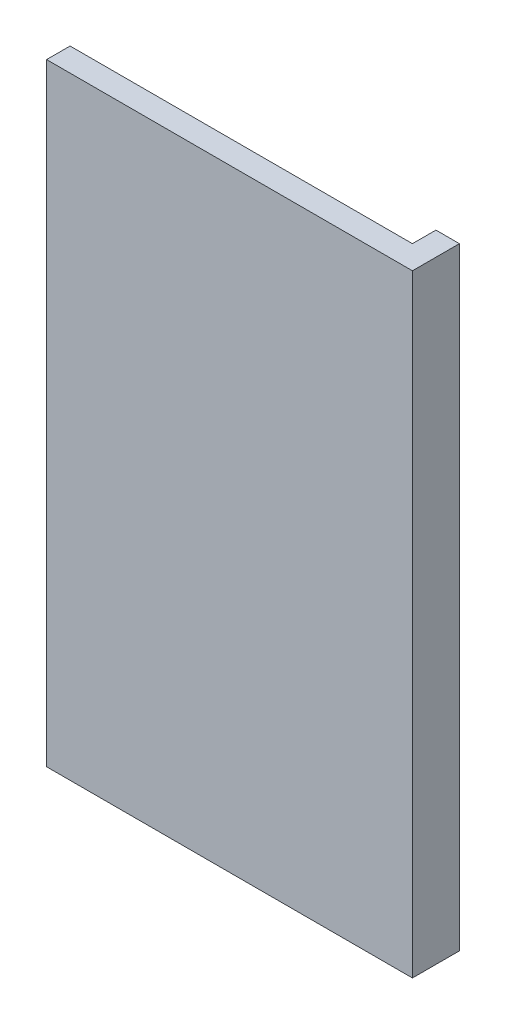
SolidWorks part; units mm, degrees
ref_plane "Front Plane" through (0, 0, 0) normal (0, 0, 1) x (1, 0, 0)
ref_plane "Top Plane" through (0, 0, 0) normal (0, 1, 0) x (1, 0, 0)
ref_plane "Right Plane" through (0, 0, 0) normal (1, 0, 0) x (0, 0, -1)
other "Configuration Table"
sketch "Sketch2" plane through (0, 0, 0) normal (0, 0, 1) x (1, 0, 0)
  line L1 (15.3819, 48) -> (-13.6181, 48)
  line L2 (15.3819, 48) -> (15.3819, -2)
  line L3 (15.3819, -2) -> (-13.6181, -2)
  line L4 (-13.6181, 48) -> (-13.6181, -2)
  line L5 (15.3819, 48) -> (15.5319, 48)
  line L6 (-13.6181, -2) -> (13.3819, -2)
  line L7 (15.3819, 0) -> (15.3819, 48)
  line L8 (15.3819, 48) -> (13.3819, 48)
  line L9 (13.3819, 48) -> (13.3819, 0)
  line L10 (13.3819, 0) -> (-13.6181, 0)
  line L11 (-13.6181, 0) -> (-13.6181, -2)
  line L12 (-13.6181, -2) -> (13.3819, -2)
  line L13 (15.3819, 0) -> (15.3819, 48)
  line L14 (15.3819, 48) -> (13.3819, 48)
  line L15 (13.3819, 48) -> (13.3819, 0)
  line L16 (13.3819, 0) -> (-13.6181, 0)
  line L17 (-13.6181, 0) -> (-13.6181, -2)
  line L18 (15.3819, 48) -> (15.3819, -2)
  line L19 (15.3819, -2) -> (15.5319, -2)
  line L20 (15.5319, 48) -> (15.5319, -2)
  line L21 (15.5319, -2) -> (-13.6181, -2)
  line L22 (15.5319, -2) -> (15.5319, -2.15)
  line L23 (15.5319, -2.15) -> (-13.6181, -2.15)
  line L24 (-13.6181, -2) -> (-13.6181, -2.15)
  line L25 (15.5319, 48) -> (17.5319, 48)
  line L26 (15.5319, 48) -> (15.5319, -2.15)
  line L27 (15.5319, -2.15) -> (17.5319, -2.15)
  line L28 (17.5319, 48) -> (17.5319, -2.15)
  line L29 (17.5319, -2.15) -> (-13.6181, -2.15)
  line L30 (17.5319, -2.15) -> (17.5319, -4.15)
  line L31 (17.5319, -4.15) -> (-13.6181, -4.15)
  line L32 (-13.6181, -2.15) -> (-13.6181, -4.15)
  arc A1 (13.3819, -2) -> (15.3819, 0) centre (13.3819, 0) ccw
  arc A2 (13.3819, -2) -> (15.3819, 0) centre (13.3819, 0) ccw
  line M12 (-13.6181, -2) -> (13.3819, -2)
  arc M13 (13.3819, -2) -> (15.3819, 0) centre (13.3819, 0) ccw
  line M14 (15.3819, 0) -> (15.3819, 48)
  line M15 (15.3819, 48) -> (13.3819, 48)
  line M16 (13.3819, 48) -> (13.3819, 0)
  line M17 (13.3819, 0) -> (-13.6181, 0)
  line M18 (-13.6181, 0) -> (-13.6181, -2)
  dimension "D2" = 0.15
  dimension "D3" = 2
  dimension "D1" = 0
extrude "Boss-Extrude1" add sketch "Sketch2" along normal blind 2 contours L1 L4 M17 M16 | M18 M12 M13 M14 M15 M16 M17 | L28 L25 L20 L22 L27 | L23 L32 L31 L30 L27 | L3 L2 M13 | L20 L5 L2 L19 M14 | L24 L23 L22 L19 L3 M12 region at (14.8039, 24, 0) region at (15.4569, 23, 0) region at (-0.1181, 24, 0) region at (14.9352, -1.5533, 0) region at (16.5319, 22.925, 0) region at (0.9569, -2.075, 0) region at (1.9569, -3.15, 0)
extrude "Boss-Extrude2" add sketch "Sketch2<4>" against normal blind 2 contours L23 L32 L31 L30 L27 | L28 L25 L20 L22 L27 region at (16.5319, 22.925, 0) region at (1.9569, -3.15, 0)
sketch "Sketch2<4>" plane through (0, 0, 0) normal (0, 0, 1) x (1, 0, 0) same geometry as "Sketch2"
equation "\"C\"=0.15"
equation "\"D2@Sketch2\"=\"C\""
